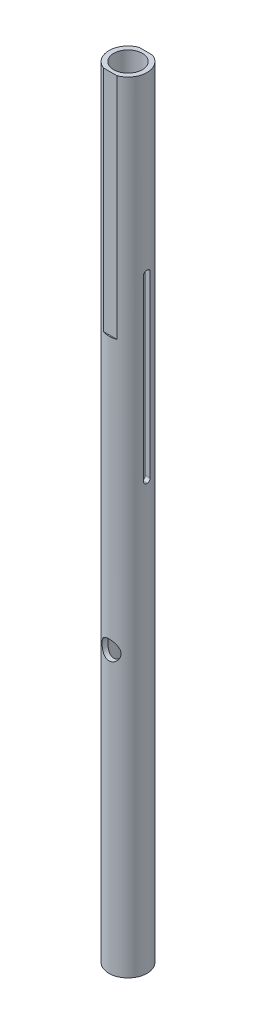
SolidWorks part; units mm, degrees
material "Plain Carbon Steel"
ref_plane "Front Plane" through (0, 0, 0) normal (0, 0, 1) x (1, 0, 0)
ref_plane "Top Plane" through (0, 0, 0) normal (0, 1, 0) x (1, 0, 0)
ref_plane "Right Plane" through (0, 0, 0) normal (1, 0, 0) x (0, 0, -1)
sketch "Sketch1" plane through (0, 0, 0) normal (0, 1, 0) x (1, 0, 0)
  circle A0 centre (0, 0) radius 15
  circle A1 centre (0, 0) radius 20
  dimension "D1" = 30
  dimension "D2" = 40
extrude "Boss-Extrude1" add sketch "Sketch1" along normal mid plane 760
ref_axis "Axis1" through (0, 380, 0) along (0, -1, 0)
sketch "Sketch8" plane through (0, -380, 0) normal (0, -1, 0) x (1, 0, 0)
  circle A1 centre (0, 0) radius 20
  circle A2 centre (0, 0) radius 20
  dimension "D2" = 40
  dimension "D1" = 0
extrude "Boss-Extrude3" add sketch "Sketch8" along normal blind 60
extrude "Cut-Extrude2" cut sketch "Sketch9" against normal blind 899.5
sketch "Sketch9" plane through (-32.3028, 416.2892, -45.2219) normal (0, 1, 0) x (-0.9769, 0, 0.2137)
  circle A0 centre (-21.8901, 51.0814) radius 15
  dimension "D1" = 30
sketch "Sketch23" plane through (0, 380, 0) normal (0, 1, 0) x (1, 0, 0)
  line L0 (0, 20) -> (0, 19.36) construction
  line L2 (-7, 18.735) -> (7, 18.735)
  line L6 (34.8937, 18.735) -> (-34.8937, 18.735) construction
  circle A0 centre (0, 0) radius 20 construction
  circle A1 centre (0, 0) radius 20
  arc A2 (7, 18.735) -> (-7, 18.735) centre (0, 0) ccw
  dimension "D1" = 14
extrude "Cut-Extrude16" cut sketch "Sketch23" against normal blind 240
mirror "Mirror1" about plane through (0, 0, 0) normal (0, 0, 1) of "Cut-Extrude16"
sketch "Sketch24" plane through (0, 0, 0) normal (1, 0, 0) x (0, 0, -1)
  line L0 (18.735, 380) -> (-18.735, 380) construction
  line L1 (-0.5, 200) -> (0.5, 200)
  line L2 (-3.5, 197) -> (-3.5, 9)
  line L3 (-0.5, 6) -> (0.5, 6)
  line L4 (3.5, 197) -> (3.5, 9)
  arc A0 (0.5, 6) -> (3.5, 9) centre (0.5, 9) ccw
  arc A1 (-3.5, 9) -> (-0.5, 6) centre (-0.5, 9) ccw
  arc A2 (0.5, 200) -> (3.5, 197) centre (0.5, 197) cw
  arc A3 (-0.5, 200) -> (-3.5, 197) centre (-0.5, 197) ccw
  point P10 (3.5, 6)
  point P15 (3.5, 200)
  dimension "D5" = 3
  dimension "D1" = 180
  dimension "D4" = 194
extrude "Cut-Extrude17" cut sketch "Sketch24" against normal blind 20 and the other way blind 20
sketch "Sketch25" plane through (0, 380, 0) normal (0, 1, 0) x (1, 0, 0)
  circle A0 centre (0, 0) radius 17.5
  circle A1 centre (0, 0) radius 17
extrude "Cut-Extrude18" [suppressed] cut sketch "Sketch25" against normal blind 480
extrude "Cut-Extrude19" cut sketch "Sketch26" against normal blind 10 and the other way blind 10
sketch "Sketch26" plane through (0, -44.3304, 18.735) normal (0, 0, 1) x (1, 0, 0)
  line L1 (0, 394.3304) -> (0, -315.6696) construction
  circle A0 centre (0, -101.157) radius 10
  dimension "D1" = 20
extrude "Cut-Extrude20" cut sketch "Sketch27" against normal blind 20 and the other way blind 30
sketch "Sketch27" plane through (0, -44.3304, -18.735) normal (0, 0, -1) x (-1, 0, 0)
  line L1 (0, 394.3304) -> (0, -315.6696) construction
  circle A0 centre (0, -273.6696) radius 3.4
  circle A1 centre (0, -288.6696) radius 3.4
  circle A2 centre (0, -288.6696) radius 6.5 construction
  circle A3 centre (0, -273.6696) radius 6.5 construction
